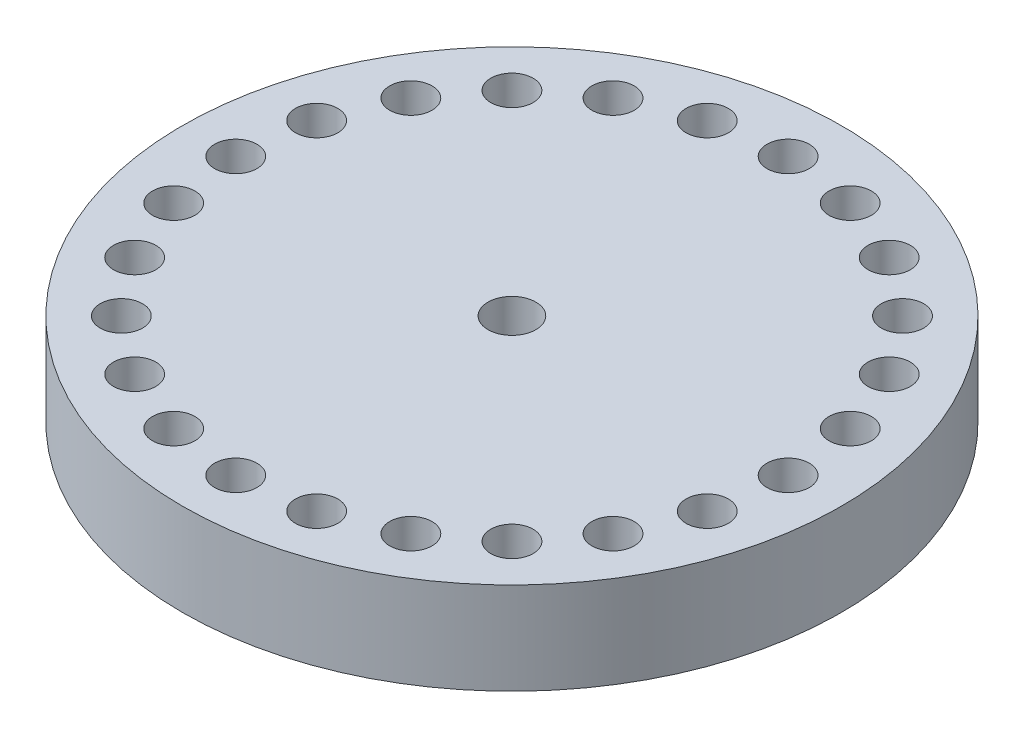
SolidWorks part; units mm, degrees
ref_plane "Front Plane" through (0, 0, 0) normal (0, 0, 1) x (1, 0, 0)
ref_plane "Top Plane" through (0, 0, 0) normal (0, 1, 0) x (1, 0, 0)
ref_plane "Right Plane" through (0, 0, 0) normal (1, 0, 0) x (0, 0, -1)
sketch "Sketch1" plane through (0, 0, 0) normal (0, 1, 0) x (1, 0, 0)
  circle A0 centre (0, 0) radius 20.066 construction
  circle A1 centre (0, 0) radius 45.466
  dimension "D1" = 25.4
extrude "Boss-Extrude1" add sketch "Sketch1" along normal blind 25.4
sketch "Sketch3" plane through (0, 0, 0) normal (0, -1, 0) x (1, 0, 0)
  circle A0 centre (0, 0) radius 19.05
  dimension "D1" = 38.1
sketch "Sketch4" plane through (0, 0, 0) normal (0, -1, 0) x (1, 0, 0)
  line L0 (0, 0) -> (0, 38.1) construction
  circle A0 centre (0, 38.1) radius 2.54
  dimension "D1" = 38.1
  dimension "D2" = 5.08
hole_wizard "CSK for 1/4 Flat Head Machine Screw1" positions "Sketch6" profile "Sketch7" countersink size "1/4" standard "ANSI Inch"
sketch "Sketch6" plane through (0, 25.4, 0) normal (0, 1, 0) x (1, 0, 0)
  point P0 (0, 0)
sketch "Sketch7" plane through (0, 25.4, 0) normal (1, 0, 0) x (0, 0, 1)
  line L0 (0, 0) -> (0, 27.3611)
  line L1 (0, 27.3611) -> (3.2639, 25.4)
  line L2 (3.2639, 25.4) -> (3.2639, 3.6524)
  line L3 (3.2639, 3.6524) -> (6.4389, 0)
  line L5 (6.4389, 0) -> (0, 0)
  line L6 (-3.2639, 3.6524) -> (-6.4389, 0) construction
  line L10 (0, 27.3611) -> (-3.2639, 25.4) construction
  line L11 (0, -6.35) -> (0, 107.95) construction
  dimension "Hole Dia." = 6.5278
  dimension "Hole Depth" = 25.4
  dimension "Near C'Sink Dia." = 12.8778
  dimension "Near C'Sink Angle" = 82
  dimension "Drill Angle" = 118
sketch "Sketch8" plane through (0, 25.4, 0) normal (0, 1, 0) x (1, 0, 0)
  circle A0 centre (0, 0) radius 46.9556
extrude "Cut-Extrude2" cut sketch "Sketch8" against normal blind 12.7
extrude "Cut-Extrude3" cut sketch "Sketch4" against normal through all
sketch "Sketch9" plane through (0, 12.7, 0) normal (0, 1, 0) x (1, 0, 0)
  circle A0 centre (0, -38.1) radius 2.921
  dimension "D1" = 5.842
extrude "Cut-Extrude4" cut sketch "Sketch9" against normal blind 5.08
sketch "Sketch10" plane through (0, 12.7, 0) normal (0, 1, 0) x (1, 0, 0)
  circle A0 centre (0, 0) radius 22.8348
sketch "Sketch11" plane through (0, 12.7, 0) normal (0, 1, 0) x (1, 0, 0)
  circle A0 centre (0, 0) radius 3.302
  dimension "D1" = 6.604
extrude "Cut-Extrude5" cut sketch "Sketch11" against normal through all
pattern_circular "CirPattern2" count 24 every 15 about axis through (0, 12.7, 0) along (0, 1, 0) of "Cut-Extrude3"
sketch "Sketch12" plane through (0, 12.7, 0) normal (0, 1, 0) x (1, 0, 0)
  circle A0 centre (0, 0) radius 38.3099
pattern_circular "CirPattern3" count 24 every 15 about axis through (0, 12.7, 0) along (0, 1, 0) of "Cut-Extrude4"
ref_axis "Axis1" through (0, 0, 0) along (0, 1, 0)
ref_plane "Plane1" through (0, 0, 0) normal (1, 0, 0) x (0, 1, 0)
sketch "Sketch13" plane through (0, 0, 0) normal (1, 0, 0) x (0, 1, 0)
  line L0 (0, 0) -> (-14.1793, 0)
  line L1 (0, 0) -> (0, 19.05)
  line L2 (0, 19.05) -> (0, -19.05) construction
  line L3 (0, 19.05) -> (-13.4727, 2.2091)
  arc A0 (-13.4727, 2.2091) -> (-14.1793, 0) centre (-10.5569, 0.0589) ccw
revolve "Revolve1" add sketch "Sketch13" angle 360 about L0
